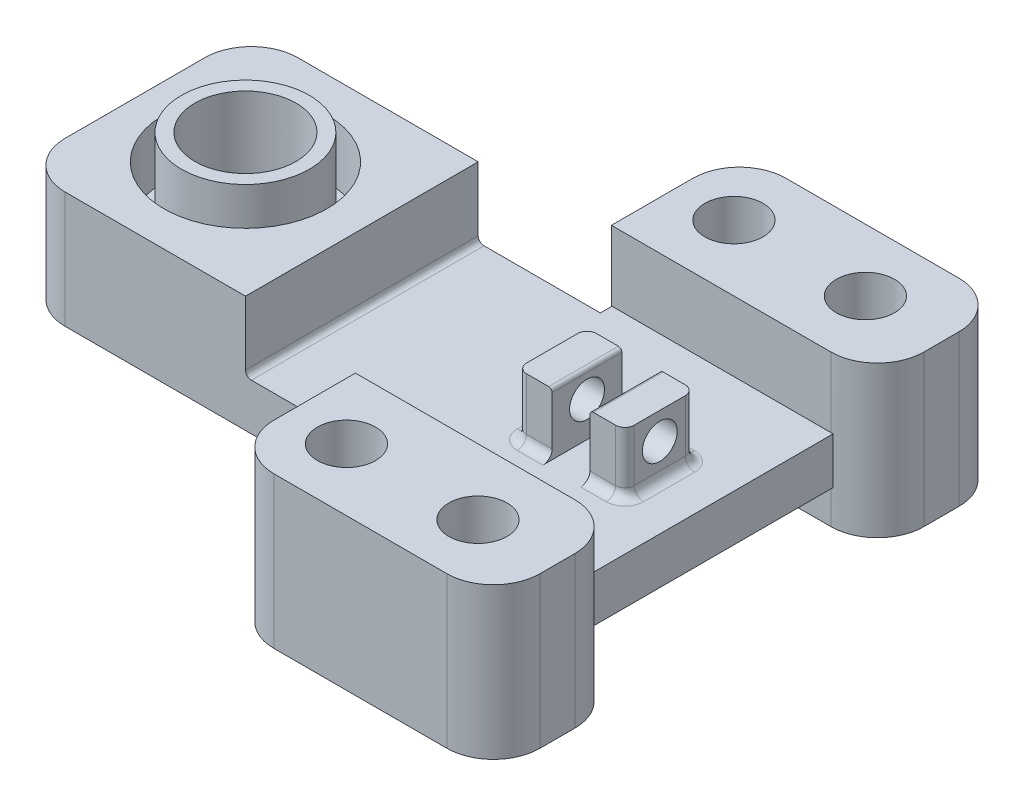
SolidWorks part; units mm, degrees
ref_plane "Front Plane" through (0, 0, 0) normal (0, 0, 1) x (1, 0, 0)
ref_plane "Top Plane" through (0, 0, 0) normal (0, 1, 0) x (1, 0, 0)
ref_plane "Right Plane" through (0, 0, 0) normal (1, 0, 0) x (0, 0, -1)
sketch "Sketch2" plane through (0, 0, 0) normal (0, 1, 0) x (1, 0, 0)
  line L1 (-14.4231, 13.5577) -> (34.5769, 13.5577)
  line L2 (-14.4231, 13.5577) -> (-14.4231, -6.4423)
  line L3 (-14.4231, -6.4423) -> (34.5769, -6.4423)
  line L4 (34.5769, 13.5577) -> (34.5769, -6.4423)
  dimension "D1" = 49
  dimension "D2" = 20
extrude "Boss-Extrude1" add sketch "Sketch2" along normal blind 10
sketch "Sketch3" plane through (0, 0, 0) normal (0, -1, 0) x (1, 0, 0)
  line L0 (34.5769, 6.4423) -> (34.5769, -13.5577) construction
  line L1 (27.5769, -5.0677) -> (-2.4231, -5.0677)
  line L2 (27.5769, -5.0677) -> (27.5769, -2.0477)
  line L3 (27.5769, -2.0477) -> (-2.4231, -2.0477)
  line L4 (-2.4231, -5.0677) -> (-2.4231, -2.0477)
  line L5 (-14.4231, -3.5577) -> (34.5769, -3.5577) construction
  line L6 (-14.4231, -13.5577) -> (-14.4231, 6.4423) construction
  dimension "D1" = 30
  dimension "D2" = 7
  dimension "D3" = 3.02
  dimension "D4" = 1.51
extrude "Cut-Extrude1" cut sketch "Sketch3" against normal blind 2
sketch "Sketch4" plane through (0, 0, 0) normal (0, -1, 0) x (1, 0, 0)
  line L0 (-2.4231, -2.0477) -> (-2.4231, -5.0677) construction
  line L1 (-2.4231, -6.5477) -> (-7.4231, -6.5477)
  line L2 (-2.4231, -6.5477) -> (-2.4231, -0.5477)
  line L3 (-2.4231, -0.5477) -> (-7.4231, -0.5477)
  line L4 (-7.4231, -6.5477) -> (-7.4231, -0.5477)
  line L6 (27.5769, -2.0477) -> (-2.4231, -2.0477) construction
  dimension "D1" = 6
  dimension "D2" = 5
  dimension "D3" = 1.5
extrude "Cut-Extrude2" cut sketch "Sketch4" against normal blind 5
sketch "Sketch5" plane through (0, 5, 0) normal (0, -1, 0) x (1, 0, 0)
  line L0 (-7.4231, -3.5477) -> (-2.4231, -3.5577) construction
  line L1 (-7.4231, -0.5477) -> (-7.4231, -6.5477) construction
  line L2 (-2.4231, -2.0477) -> (-2.4231, -5.0677) construction
  circle A0 centre (-4.9231, -3.5527) radius 7
  dimension "D1" = 14
extrude "Cut-Extrude3" cut sketch "Sketch5" against normal through all
sketch "Sketch12" plane through (0, 0, 0) normal (0, -1, 0) x (1, 0, 0)
  line L1 (-7.4231, -0.5477) -> (-2.4231, -0.5477)
  line L2 (-7.4231, -0.5477) -> (-7.4231, -6.5477)
  line L3 (-7.4231, -6.5477) -> (-2.4231, -6.5477)
  line L4 (-2.4231, -0.5477) -> (-2.4231, -6.5477)
extrude "Boss-Extrude4" add sketch "Sketch12" against normal blind 0.8
sketch "Sketch14" plane through (0, 0, 6.4423) normal (0, 0, 1) x (1, 0, 0)
  line L0 (-14.4231, 10) -> (34.5769, 10) construction
  line L1 (5.0769, 10) -> (34.5769, 10)
  line L2 (5.0769, 10) -> (5.0769, 4)
  line L3 (5.0769, 4) -> (34.5769, 4)
  line L4 (34.5769, 10) -> (34.5769, 4)
  line L5 (34.5769, 10) -> (34.5769, 0) construction
  line L6 (27.5769, 2) -> (-2.4231, 2) construction
  line L7 (2.0769, 5) -> (2.0769, 10) construction
  dimension "D1" = 2
  dimension "D2" = 3
extrude "Cut-Extrude6" cut sketch "Sketch14" against normal through all
sketch "Sketch20" plane through (0, 0.8, 0) normal (0, 1, 0) x (1, 0, 0)
  line L0 (-2.4231, 0.5477) -> (-7.4231, 0.5477) construction
  line L1 (-7.4231, 6.5477) -> (-2.4231, 6.5477)
  line L2 (-7.4231, 6.5477) -> (-7.4231, 0.5477)
  line L3 (-7.4231, 0.5477) -> (-2.4231, 0.5477)
  line L4 (-2.4231, 6.5477) -> (-2.4231, 0.5477)
  line L5 (-2.4231, 0.5477) -> (-7.4231, 0.5477) construction
extrude "Boss-Extrude6" add sketch "Sketch20" along normal up to surface (4.2 mm away) up to face at (-4.9231, 5, -10.5527)
sketch "Sketch21" plane through (0, 5, 0) normal (0, 1, 0) x (1, 0, 0)
  circle A0 centre (-4.9231, 3.5527) radius 4.6
  dimension "D1" = 9.2
extrude "Cut-Extrude8" cut sketch "Sketch21" against normal blind 0.5
sketch "Sketch22" plane through (0, 4.5, 0) normal (0, 1, 0) x (1, 0, 0)
  circle A0 centre (-4.9231, 3.5527) radius 3.825
  dimension "D1" = 7.65
extrude "Cut-Extrude9" cut sketch "Sketch22" against normal blind 4
sketch "Sketch24" plane through (0, 5, 0) normal (0, 1, 0) x (1, 0, 0)
  circle A0 centre (-4.9231, 3.5527) radius 4.25
  circle A1 centre (-4.9231, 3.5527) radius 4.6
  dimension "D1" = 9.2
  dimension "D2" = 8.5
extrude "Cut-Extrude11" cut sketch "Sketch24" against normal blind 1
sketch "Sketch26" plane through (0, 4.5, 0) normal (0, 1, 0) x (1, 0, 0)
  circle A0 centre (-4.9231, 3.5527) radius 3.825
  circle A1 centre (-4.9231, 3.5527) radius 4.25
extrude "Boss-Extrude9" add sketch "Sketch26" along normal blind 0.5
sketch "Sketch27" plane through (0, 5, 0) normal (0, 1, 0) x (1, 0, 0)
  circle A0 centre (-4.9231, 3.5527) radius 4.6
  circle A1 centre (-4.9231, 3.5527) radius 7
extrude "Cut-Extrude12" cut sketch "Sketch27" against normal blind 1
sketch "Sketch39" plane through (0, 4, 0) normal (0, 1, 0) x (1, 0, 0)
  line L0 (5.0769, 3.5577) -> (29.0295, 3.5577) construction
  line L1 (5.0769, 13.5577) -> (5.0769, -6.4423) construction
  line L4 (6.3269, -0.6923) -> (6.3269, 8.9673) construction
  line L5 (5.0769, 13.5577) -> (5.0769, -6.4423) construction
  circle A0 centre (6.3269, -0.6923) radius 0.6
  circle A1 centre (7.5769, 7.8077) radius 0.6
  circle A2 centre (9.9936, 7.8077) radius 0.6
  circle A3 centre (8.7436, -0.6923) radius 0.6
  circle A4 centre (12.4103, 7.8077) radius 0.6
  circle A5 centre (11.1603, -0.6923) radius 0.6
  circle A6 centre (14.8269, 7.8077) radius 0.6
  circle A7 centre (13.5769, -0.6923) radius 0.6
  circle A8 centre (17.2436, 7.8077) radius 0.6
  circle A9 centre (15.9936, -0.6923) radius 0.6
  circle A10 centre (19.6603, 7.8077) radius 0.6
  circle A11 centre (18.4103, -0.6923) radius 0.6
  circle A12 centre (22.0769, 7.8077) radius 0.6
  circle A13 centre (20.8269, -0.6923) radius 0.6
  circle A22 centre (24.4936, 7.8077) radius 0.6 [skipped]
  circle A23 centre (23.2436, -0.6923) radius 0.6 [skipped]
  dimension "D1" = 1.2
  dimension "D2" = 1.2
  dimension "D7" = 1.25
  dimension "D3" = 8.5
  dimension "D4" = 1.25
  dimension "D5" = 4.25
  dimension "D6" = 8
fillet "Fillet1" radius 0.5 1 edges at (5.0769, 4, -3.5577)
sketch "Sketch56" plane through (0, 0, 0) normal (0, -1, 0) x (1, 0, 0)
  line L0 (27.5769, -2.0477) -> (-2.4231, -2.0477) construction
  line L1 (-2.4231, -5.0677) -> (-2.4231, -2.0477) construction
  circle A0 centre (28.9269, -3.5577) radius 2
  dimension "D1" = 4
  dimension "D2" = 1.51
  dimension "D3" = 31.35
extrude "Cut-Extrude13" cut sketch "Sketch56" against normal up to surface (2 mm away) up to face at (13.1618, 2, -3.5578)
sketch "Sketch57" plane through (0, 4, 0) normal (0, 1, 0) x (1, 0, 0)
  line L0 (26.0569, 11.0577) -> (26.0569, -3.9423) construction
  line L1 (24.4319, 0.5577) -> (21.4319, 0.5577)
  line L2 (30.6819, 0.5577) -> (27.6819, 0.5577)
  line L3 (30.6819, 0.5577) -> (30.6819, 6.5577)
  line L4 (30.6819, 6.5577) -> (27.6819, 6.5577)
  line L5 (27.6819, 0.5577) -> (27.6819, 6.5577)
  line L6 (30.6819, 0.5577) -> (27.6819, 6.5577) construction
  line L7 (30.6819, 6.5577) -> (27.6819, 0.5577) construction
  line L8 (24.4319, 0.5577) -> (24.4319, 6.5577)
  line L9 (24.4319, 6.5577) -> (21.4319, 6.5577)
  line L10 (21.4319, 0.5577) -> (21.4319, 6.5577)
  line L11 (24.4319, 0.5577) -> (21.4319, 6.5577) construction
  line L12 (24.4319, 6.5577) -> (21.4319, 0.5577) construction
  line L13 (5.5769, 13.5577) -> (5.5769, -6.4423) construction
  line L14 (5.5769, 13.5577) -> (34.5769, 13.5577) construction
  circle A1 centre (26.0569, 3.5577) radius 6
  circle A2 centre (26.0569, 3.5577) radius 5.8
  point P6 (26.0569, 3.5577)
  point P7 (29.1819, 3.5577)
  point P19 (22.9319, 3.5577)
  dimension "D1" = 11.6
  dimension "D2" = 0.2
  dimension "D3" = 15
  dimension "D4" = 3
  dimension "D11" = 20.48
  dimension "D5" = 6
  dimension "D6" = 3.125
  dimension "D7" = 3.125
  dimension "D8" = 6
  dimension "D9" = 3
  dimension "D10" = 20.48
  dimension "D12" = 10
extrude "Boss-Extrude19" add sketch "Sketch57" along normal blind 5.3 contours L5 L2 L3 L4 | L10 L1 L8 L9 region at (22.9319, 4, -3.5577) region at (29.1819, 4, -3.5577)
sketch "Sketch58" plane through (30.6819, 0, 0) normal (1, 0, 0) x (0, 0, -1)
  line L2 (0.5577, 4) -> (6.5577, 4) construction
  line L3 (0.5577, 9.3) -> (0.5577, 4) construction
  circle A0 centre (3.5577, 7) radius 1.5
  dimension "D1" = 3
  dimension "D2" = 3
  dimension "D3" = 3
extrude "Cut-Extrude14" cut sketch "Sketch58" against normal up to surface (9.25 mm away) up to face at (21.4319, 6.65, -3.5577)
fillet "Fillet2" radius 0.3 2 edges at (24.4319, 9.3, -3.5577) (27.6819, 9.3, -3.5577)
fillet "Fillet3" radius 0.8 10 edges at (21.4319, 6.65, -0.5577) (21.4319, 6.65, -6.5577) (21.4319, 4, -3.5577) (22.9319, 4, -6.5577) (30.6819, 6.65, -6.5577) (29.1819, 4, -6.5577) (30.6819, 6.65, -0.5577) (30.6819, 4, -3.5577) (29.1819, 4, -0.5577) (22.9319, 4, -0.5577)
ref_plane "Plane1" through (0, 0, -3.5577) normal (0, 0, -1) x (-1, 0, 0)
sketch "Sketch60" plane through (0, 0, -13.5577) normal (0, 0, -1) x (-1, 0, 0)
  line L1 (-34.5769, 4) -> (-15.5769, 4)
  line L2 (-34.5769, 4) -> (-34.5769, 0)
  line L3 (-34.5769, 0) -> (-15.5769, 0)
  line L4 (-15.5769, 4) -> (-15.5769, 0)
  line L5 (-34.5769, 0) -> (14.4231, 0) construction
  dimension "D1" = 19
extrude "Boss-Extrude21" add sketch "Sketch60" along normal blind 1
sketch "Sketch59" plane through (0, 0, -14.5577) normal (0, 0, -1) x (-1, 0, 0)
  line L0 (-15.5769, 0) -> (14.4231, 0) construction
  line L1 (-38.3869, -3) -> (-15.5269, -3)
  line L2 (-38.3869, -3) -> (-38.3869, 10)
  line L3 (-38.3869, 10) -> (-15.5269, 10)
  line L4 (-15.5269, -3) -> (-15.5269, 10)
  line L5 (-34.5769, 4) -> (-34.5769, 0) construction
  dimension "D1" = 22.86
  dimension "D2" = 13
  dimension "D3" = 3
  dimension "D4" = 3.81
extrude "Boss-Extrude20" add sketch "Sketch59" along normal blind 11
ref_axis "Axis1" through (28.9269, 2, -3.5577) along (0, -1, 0)
mirror "Mirror4" about plane through (0, 0, -3.5577) normal (0, 0, -1) of "Boss-Extrude20", "Boss-Extrude21"
sketch "Sketch61" plane through (0, 10, 0) normal (0, 1, 0) x (1, 0, 0)
  line L0 (24.4319, 7.3577) -> (24.4319, 20.2077) construction
  line L1 (-14.4231, 3.5577) -> (34.5769, 3.5577) construction
  line L2 (-14.4231, 13.5577) -> (-14.4231, -6.4423) construction
  line L3 (34.5769, 14.5577) -> (34.5769, -7.4423) construction
  line L4 (24.4319, 20.2077) -> (20.4069, 20.2077) construction
  line L5 (27.6819, 7.3577) -> (27.6819, 20.2077) construction
  line L6 (27.6819, 20.2077) -> (31.7069, 20.2077) construction
  line L7 (27.6819, -13.0923) -> (31.7069, -13.0923) construction
  line L8 (27.6819, -0.2423) -> (27.6819, -13.0923) construction
  line L9 (24.4319, -13.0923) -> (20.4069, -13.0923) construction
  line L10 (24.4319, -0.2423) -> (24.4319, -13.0923) construction
  circle A0 centre (20.4069, 20.2077) radius 2.5
  circle A1 centre (31.7069, 20.2077) radius 2.5
  circle A2 centre (31.7069, -13.0923) radius 2.5
  circle A3 centre (20.4069, -13.0923) radius 2.5
  dimension "D3" = 5
  dimension "D2" = 11.3
  dimension "D4" = 16.65
extrude "Cut-Extrude15" cut sketch "Sketch61" against normal up to next
fillet "Fillet4" radius 4 8 edges at (38.3869, 3.5, -25.5577) (38.3869, 3.5, 7.4423) (38.3869, 3.5, 18.4423) (15.5269, 3.5, 18.4423) (15.5269, 3.5, -25.5577) (-14.4231, 5, -13.5577) (-14.4231, 5, 6.4423) (38.3869, 3.5, -14.5577)
sketch "Sketch65" plane through (0, 4, 0) normal (0, 1, 0) x (1, 0, 0)
  circle A0 centre (-4.9231, 3.5527) radius 4.25 construction
  circle A1 centre (-4.9231, 3.5527) radius 7
  circle A2 centre (-4.9231, 3.5527) radius 7
  circle A3 centre (-4.9231, 3.5527) radius 4.25
  dimension "D1" = 0
extrude "Boss-Extrude24" add sketch "Sketch65" along normal up to surface (1 mm away) up to face at (-4.9231, 5, 0.6973)
sketch "Sketch66" plane through (0, 5, 0) normal (0, 1, 0) x (1, 0, 0)
  circle A0 centre (-4.9231, 3.5527) radius 4.35
  dimension "D1" = 8.7
extrude "Cut-Extrude17" cut sketch "Sketch66" against normal up to surface (4.5 mm away) contours A0 up to face at (-3.7507, 0.5, -3.5551)
sketch "Sketch67" plane through (0, 5, 0) normal (0, 1, 0) x (1, 0, 0)
  circle A0 centre (-4.9231, 3.5527) radius 5.5
  circle A1 centre (-4.9231, 3.5527) radius 4.35 construction
  circle A2 centre (-4.9231, 3.5527) radius 4.35
  dimension "D1" = 11
extrude "Boss-Extrude25" add sketch "Sketch67" along normal blind 7.2
